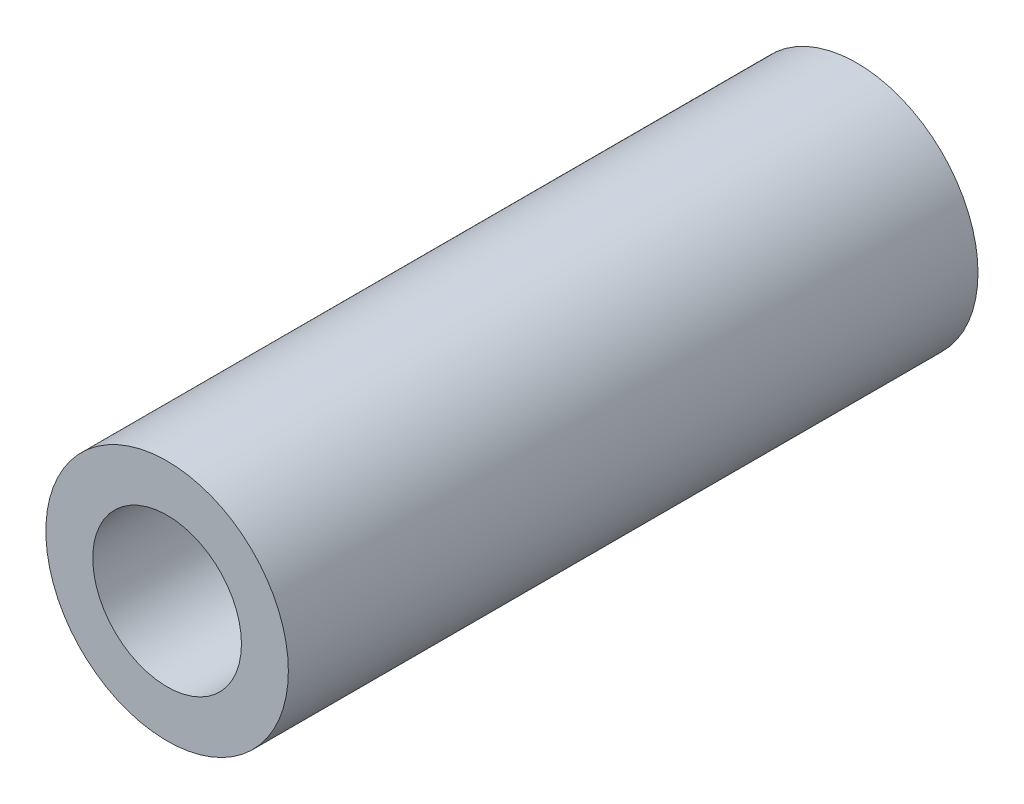
SolidWorks part; units mm, degrees
ref_plane "Front Plane" through (0, 0, 0) normal (0, 0, 1) x (1, 0, 0)
ref_plane "Top Plane" through (0, 0, 0) normal (0, 1, 0) x (1, 0, 0)
ref_plane "Right Plane" through (0, 0, 0) normal (1, 0, 0) x (0, 0, -1)
sketch "Sketch1" plane through (0, 0, 0) normal (0, 0, 1) x (1, 0, 0)
  circle A0 centre (0, 0) radius 4.025
  circle A1 centre (0, 0) radius 6.565
  dimension "D1" = 8.05
  dimension "D2" = 2.54
extrude "Boss-Extrude1" add sketch "Sketch1" along normal blind 37.338
